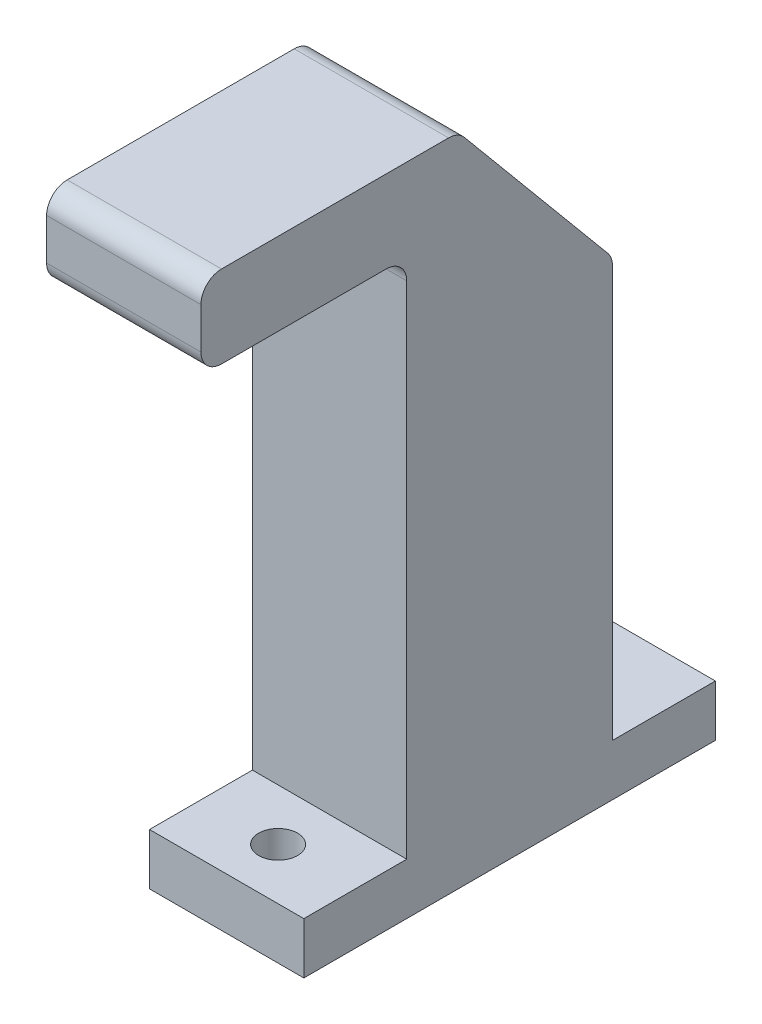
SolidWorks part; units mm, degrees
ref_plane "Front Plane" through (0, 0, 0) normal (0, 0, 1) x (1, 0, 0)
ref_plane "Top Plane" through (0, 0, 0) normal (0, 1, 0) x (1, 0, 0)
ref_plane "Right Plane" through (0, 0, 0) normal (1, 0, 0) x (0, 0, -1)
sketch "Sketch1" plane through (0, 0, 0) normal (1, 0, 0) x (0, 0, -1)
  line L0 (0, 0) -> (0, 8)
  line L1 (0, 8) -> (25, 8)
  line L4 (40, -10) -> (40, -55.68)
  line L5 (40, -55.68) -> (20, -55.68)
  line L6 (20, -55.68) -> (20, 0)
  line L7 (20, 0) -> (0, 0)
  line L8 (25, 8) -> (40, -10)
  dimension "D1" = 55.68
  dimension "D2" = 8
  dimension "D3" = 20
  dimension "D4" = 25
  dimension "D5" = 20
  dimension "D6" = 45.68
extrude "Boss-Extrude1" add sketch "Sketch1" along normal mid plane 15
sketch "Sketch2" plane through (0, 8, 0) normal (0, 1, 0) x (1, 0, 0)
  line L0 (-7.5, 40) -> (-7.5, 25) construction
  line L1 (7.5, 40) -> (7.5, 25) construction
  line L2 (7.5, 25) -> (-7.5, 25) construction
  circle A0 centre (-4, 31) radius 2
  circle A1 centre (4, 31) radius 2
  dimension "D1" = 4
  dimension "D2" = 4
  dimension "D6" = 6
  dimension "D3" = 3.5
  dimension "D4" = 3.5
  dimension "D5" = 6
sketch "Sketch3" plane through (0, 8, 0) normal (0, 1, 0) x (1, 0, 0)
  circle A0 centre (-4, 31) radius 1.05
  circle A1 centre (4, 31) radius 1.05
  dimension "D1" = 2.1
  dimension "D2" = 2.1
fillet "Fillet1" radius 2 5 edges at (0, -10, -40) (0, 8, -25) (0, 8, 0) (0, 0, 0) (0, 0, -20)
sketch "Sketch4" plane through (0, -55.68, 0) normal (0, -1, 0) x (1, 0, 0)
  line L0 (7.5, -40) -> (-7.5, -40)
  line L1 (7.5, -40) -> (7.5, -50)
  line L2 (-7.5, -40) -> (-7.5, -50)
  line L3 (7.5, -50) -> (-7.5, -50)
  line L4 (7.5, -20) -> (-7.5, -20)
  line L5 (7.5, -20) -> (7.5, -10)
  line L6 (-7.5, -20) -> (-7.5, -10)
  line L7 (7.5, -10) -> (-7.5, -10)
  circle A0 centre (0, -45) radius 1.6
  circle A1 centre (0, -15) radius 1.8908
  dimension "D3" = 3.2
  dimension "D4" = 3.7816
  dimension "D5" = 5
  dimension "D6" = 5
  dimension "D1" = 10
  dimension "D2" = 10
extrude "Boss-Extrude2" add sketch "Sketch4" against normal blind 5
